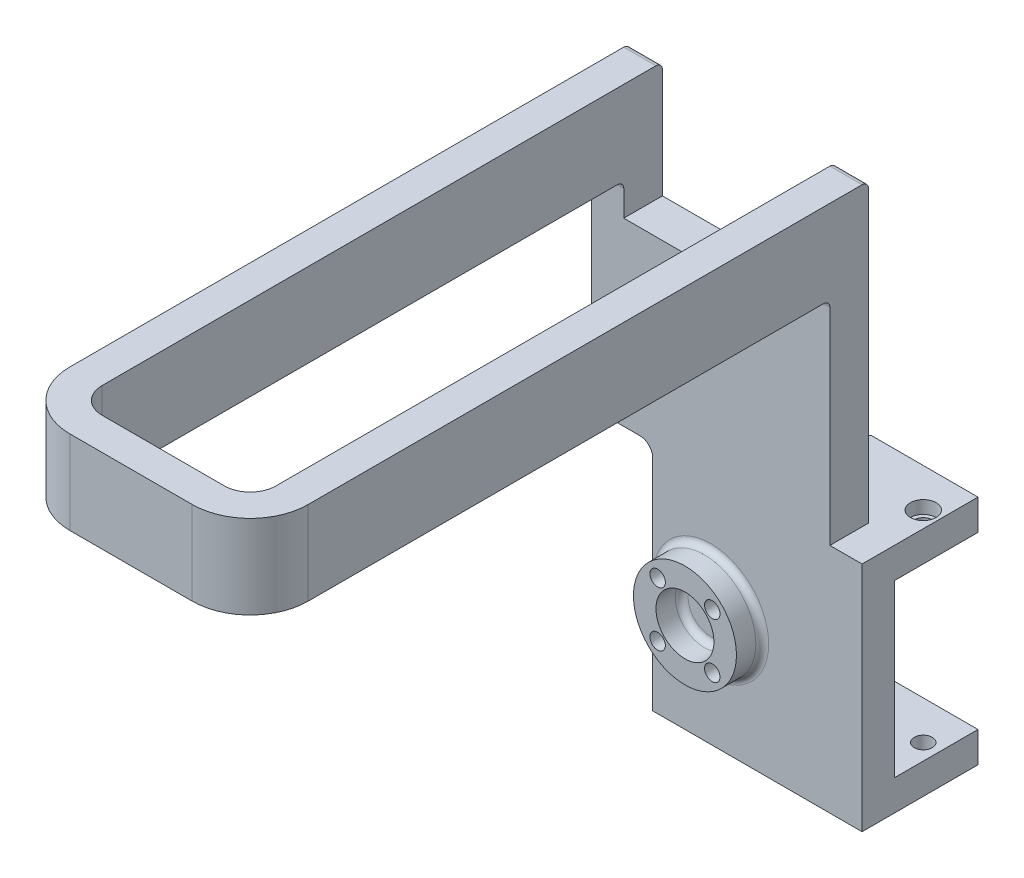
SolidWorks part; units mm, degrees
ref_plane "正面" through (0, 0, 0) normal (0, 0, 1) x (1, 0, 0)
ref_plane "平面" through (0, 0, 0) normal (0, 1, 0) x (1, 0, 0)
ref_plane "右側面" through (0, 0, 0) normal (1, 0, 0) x (0, 0, -1)
sketch "ｽｹｯﾁ1" plane through (0, 0, 0) normal (0, 0, 1) x (1, 0, 0)
  line L1 (-16.25, 18) -> (16.25, 18)
  line L2 (-16.25, 18) -> (-16.25, -18)
  line L3 (-16.25, -18) -> (16.25, -18)
  line L4 (16.25, 18) -> (16.25, -18)
  line L5 (-16.25, 18) -> (16.25, -18) construction
  line L6 (-16.25, -18) -> (16.25, 18) construction
  point P0 (0, 0)
  dimension "D1" = 36
  dimension "D2" = 32.5
extrude "ﾎﾞｽ - 押し出し1" add sketch "ｽｹｯﾁ1" along normal blind 18
sketch "ｽｹｯﾁ2" plane through (16.25, 0, 0) normal (1, 0, 0) x (0, 0, -1)
  line L0 (0, -18) -> (0, 18) construction
  line L1 (0, 13.25) -> (-13, 13.25)
  line L2 (0, 13.25) -> (0, -13.25)
  line L3 (0, -13.25) -> (-13, -13.25)
  line L4 (-13, 13.25) -> (-13, -13.25)
  line L5 (-18, -18) -> (-18, 18) construction
  point P6 (0, 0)
  point P8 (0, 0)
  dimension "D1" = 26.5
  dimension "D2" = 5
extrude "ｶｯﾄ - 押し出し1" cut sketch "ｽｹｯﾁ2" against normal through all
hole_wizard "M2 丸平ねじ用座ぐり穴3" positions "ｽｹｯﾁ5" profile "ｽｹｯﾁ6" counterbore size "M2" standard "JIS"
sketch "ｽｹｯﾁ5" plane through (0, 18, 0) normal (0, -1, 0) x (1, 0, 0)
  line L0 (-16.25, 13) -> (16.25, 13) construction
  line L1 (16.25, 0) -> (16.25, 13) construction
  point P0 (13.75, 6)
  point P2 (-7.25, 6)
  dimension "D1" = 7
  dimension "D2" = 2.5
  dimension "D3" = 23.5
sketch "ｽｹｯﾁ6" plane through (13.75, 18, 6) normal (1, 0, 0) x (0, 0, 1)
  line L0 (0, 0) -> (0, 5.5912)
  line L1 (0, 5.5912) -> (1.4, 4.75)
  line L2 (1.4, 4.75) -> (1.4, 2)
  line L3 (1.4, 2) -> (2, 2)
  line L4 (2, 2) -> (2, 0)
  line L5 (2, 0) -> (0, 0)
  line L10 (0, 5.5912) -> (-1.4, 4.75) construction
  line L11 (0, -6.35) -> (0, 107.95) construction
  dimension "穴の直径" = 2.8
  dimension "穴の深さ" = 4.75
  dimension "座ぐり穴の直径" = 4
  dimension "座ぐり穴の深さ" = 2
  dimension "ﾄﾞﾘﾙ角度" = 118
mirror "ﾐﾗｰ1" about plane through (0, 0, 0) normal (0, 1, 0) of "M2 丸平ねじ用座ぐり穴3"
sketch "ｽｹｯﾁ4" plane through (0, 13.25, 0) normal (0, -1, 0) x (1, 0, 0)
  circle A0 centre (-7.25, -4.5) radius 8.25
  circle A2 centre (-7.25, 6) radius 2 construction
  circle A3 centre (-7.25, 6) radius 1.2
  dimension "D1" = 16.5
  dimension "D2" = 10.5
extrude "ｶｯﾄ - 押し出し3" cut sketch "ｽｹｯﾁ4" against normal through all both and the other way through all
sketch "ｽｹｯﾁ18" plane through (0, 0, 18) normal (0, 0, 1) x (1, 0, 0)
  line L1 (-16.25, 18) -> (-16.25, -18) construction
  line L3 (16.25, -18) -> (16.25, 18) construction
  circle A0 centre (-7.25, 0) radius 8
  point P8 (-16.25, 0)
  dimension "D1" = 16
  dimension "D2" = 23.5
extrude "ﾎﾞｽ - 押し出し4" add sketch "ｽｹｯﾁ18" along normal blind 4
hole_wizard "M2 丸平ねじ用座ぐり穴2" positions "ｽｹｯﾁ11" profile "ｽｹｯﾁ12" counterbore size "M2" standard "JIS" end condition through all
sketch "ｽｹｯﾁ11" plane through (0, 0, 13) normal (0, 0, -1) x (-1, 0, 0)
  line L1 (11.4926, 4.2426) -> (3.0074, 4.2426)
  line L2 (11.4926, 4.2426) -> (11.4926, -4.2426)
  line L3 (11.4926, -4.2426) -> (3.0074, -4.2426)
  line L4 (3.0074, 4.2426) -> (3.0074, -4.2426)
  line L5 (-16.25, 13.25) -> (-16.25, -13.25) construction
  point P2 (11.4926, 4.2426)
  point P3 (3.0074, -4.2426)
  point P196 (11.4926, -4.2426)
  point P197 (3.0074, 4.2426)
  point P199 (3.0074, 0)
  point P210 (7.25, 4.2426)
  dimension "D1" = 12
  dimension "D2" = 23.5
sketch "ｽｹｯﾁ12" plane through (-11.4926, 4.2426, 13) normal (1, 0, 0) x (0, 1, 0)
  line L0 (0, 0) -> (0, 9)
  line L1 (0, 9) -> (1.2, 9)
  line L3 (1.2, 9) -> (1.2, 1.45)
  line L4 (1.2, 1.45) -> (2.1, 1.45)
  line L5 (2.1, 1.45) -> (2.1, 0)
  line L7 (2.1, 0) -> (0, 0)
  line L11 (0, -6.35) -> (0, 107.95) construction
  dimension "通し穴の直径" = 2.4
  dimension "通し穴の深さ" = 9
  dimension "座ぐり穴の直径" = 4.2
  dimension "座ぐり穴の深さ" = 1.45
sketch "ｽｹｯﾁ19" plane through (0, 0, 22) normal (0, 0, 1) x (1, 0, 0)
  circle A0 centre (-7.25, 0) radius 4.5
  dimension "D1" = 9
extrude "ｶｯﾄ - 押し出し9" cut sketch "ｽｹｯﾁ19" against normal up to surface (4 mm away) up to face at (0.75, 0, 18)
sketch "ｽｹｯﾁ13" plane through (0, 18, 0) normal (0, 1, 0) x (1, 0, 0)
  line L1 (-25.75, -18) -> (11.25, -18)
  line L2 (-25.75, -18) -> (-25.75, -12)
  line L3 (-25.75, -12) -> (11.25, -12)
  line L4 (11.25, -18) -> (11.25, -12)
  line L6 (16.25, -18) -> (-16.25, -18) construction
  arc A0 (-14.1647, 0) -> (-0.3353, 0) centre (-7.25, 4.5) ccw construction
  point P10 (-7.25, -3.75)
  point P11 (-7.25, -12)
  dimension "D1" = 6
  dimension "D2" = 37
extrude "ﾎﾞｽ - 押し出し3" add sketch "ｽｹｯﾁ13" along normal blind 33
sketch "ｽｹｯﾁ20" plane through (0, 51, 0) normal (0, 1, 0) x (1, 0, 0)
  line L0 (11.25, -12) -> (11.25, -99)
  line L1 (2.25, -108) -> (-16.75, -108)
  line L2 (-25.75, -99) -> (-25.75, -12)
  line L3 (-25.75, -12) -> (-20.75, -12)
  line L4 (-20.75, -12) -> (-20.75, -99)
  line L5 (-16.75, -103) -> (2.25, -103)
  line L6 (6.25, -99) -> (6.25, -12)
  line L7 (6.25, -12) -> (11.25, -12)
  line L8 (11.25, -12) -> (-16.25, -12) construction
  line L9 (-25.75, -12) -> (-25.75, -18) construction
  line L10 (11.25, -12) -> (-25.75, -12) construction
  arc A0 (11.25, -99) -> (2.25, -108) centre (2.25, -99) cw
  arc A1 (-16.75, -108) -> (-25.75, -99) centre (-16.75, -99) cw
  arc A2 (-20.75, -99) -> (-16.75, -103) centre (-16.75, -99) ccw
  arc A3 (2.25, -103) -> (6.25, -99) centre (2.25, -99) ccw
  arc A5 (-14.1647, 0) -> (-0.3353, 0) centre (-7.25, 4.5) ccw construction
  point P25 (-7.25, -3.75)
  point P26 (-7.25, -103)
  dimension "D5" = 4
  dimension "D1" = 5
  dimension "D3" = 87
extrude "ﾎﾞｽ - 押し出し5" add sketch "ｽｹｯﾁ20" along normal blind 13
fillet "ﾌｨﾚｯﾄ1" radius 1 2 edges at (8.75, 51, 18) (-23.25, 51, 18)
fillet "ﾌｨﾚｯﾄ2" radius 1 2 edges at (8.75, 64, 12) (-23.25, 64, 12)
fillet "ﾌｨﾚｯﾄ3" radius 2 1 edges at (-16.25, 18, 15)
fillet "ﾌｨﾚｯﾄ4" radius 1 2 edges at (0.75, 0, 18) (-2.75, 0, 18)
sketch "ｽｹｯﾁ21" plane through (0, 51, 0) normal (0, 1, 0) x (1, 0, 0)
  line L1 (6.25, -12) -> (-20.75, -12)
  line L2 (6.25, -12) -> (6.25, -18)
  line L3 (6.25, -18) -> (-20.75, -18)
  line L4 (-20.75, -12) -> (-20.75, -18)
extrude "ｶｯﾄ - 押し出し10" cut sketch "ｽｹｯﾁ21" against normal blind 5
